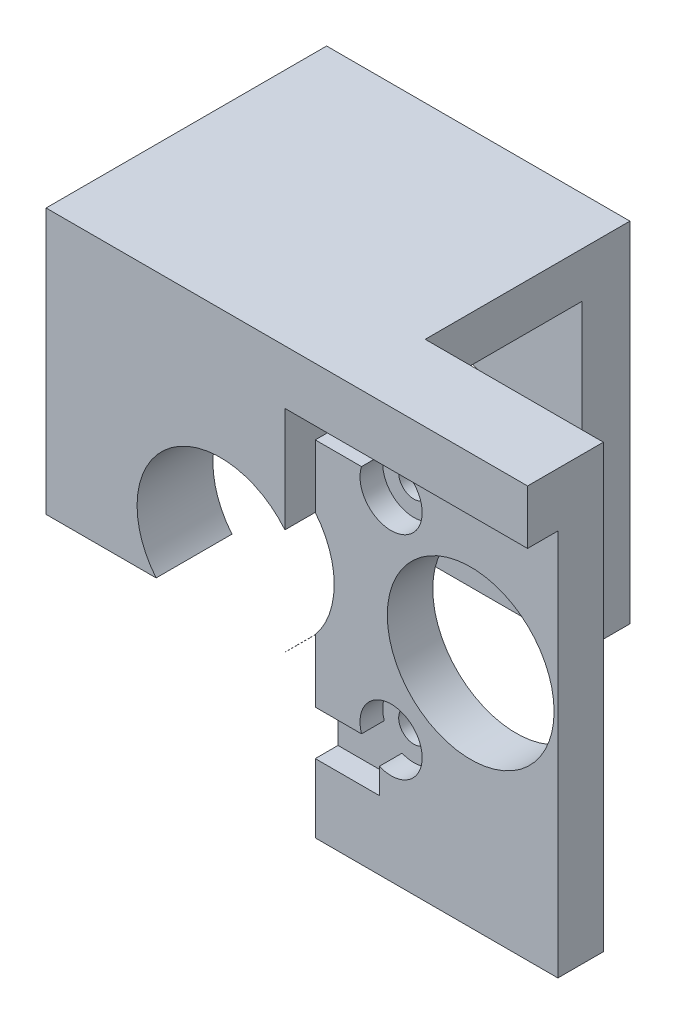
SolidWorks part; units mm, degrees
material "ABS"
ref_plane "Front Plane" through (0, 0, 0) normal (0, 0, 1) x (1, 0, 0)
ref_plane "Top Plane" through (0, 0, 0) normal (0, 1, 0) x (1, 0, 0)
ref_plane "Right Plane" through (0, 0, 0) normal (1, 0, 0) x (0, 0, -1)
sketch "Sketch1" plane through (0, 0, 0) normal (0, 0, 1) x (1, 0, 0)
  line L1 (-76.1871, 64.9281) -> (16.8129, 64.9281)
  line L2 (-76.1871, 64.9281) -> (-76.1871, -35.0719)
  line L3 (-76.1871, -35.0719) -> (16.8129, -35.0719)
  line L4 (16.8129, 64.9281) -> (16.8129, -35.0719)
  dimension "D1" = 93
  dimension "D2" = 100
extrude "Boss-Extrude2" add sketch "Sketch1" along normal blind 10 contours L1 L4 L3 L2
sketch "Sketch3" plane through (0, 0, 0) normal (0, 0, -1) x (-1, 0, 0)
  line L0 (76.1871, -35.0719) -> (-16.8129, -35.0719) construction
  line L1 (-16.8129, 64.9281) -> (-6.8129, 64.9281)
  line L2 (-16.8129, 64.9281) -> (-16.8129, -35.0719)
  line L3 (-16.8129, -35.0719) -> (-6.8129, -35.0719)
  line L4 (-6.8129, 64.9281) -> (-6.8129, -35.0719)
  line L5 (-16.8129, 64.9281) -> (-16.8129, -35.0719) construction
  dimension "D1" = 0
  dimension "D2" = 0
  dimension "D3" = 10
  dimension "D4" = 100
sketch "Sketch4" plane through (16.8129, 0, 0) normal (1, 0, 0) x (0, 0, -1)
  line L0 (-10, 64.9281) -> (-10, -35.0719) construction
  line L1 (-10, -5.0719) -> (0.01, -5.0719)
  line L2 (-10, -5.0719) -> (-10, -20.0719)
  line L3 (-10, -20.0719) -> (0.01, -20.0719)
  line L4 (0.01, -5.0719) -> (0.01, -20.0719)
  line L6 (-10, -35.0719) -> (0, -35.0719) construction
  dimension "D1" = 15
  dimension "D2" = 15
extrude "Boss-Extrude4" add sketch "Sketch4" along normal blind 24
sketch "Sketch5" plane through (0, -5.0719, 0) normal (0, 1, 0) x (1, 0, 0)
  line L0 (40.8129, -10) -> (16.8129, -10) construction
  line L2 (16.8129, 0) -> (16.8129, -10) construction
  circle A0 centre (26.8129, -5) radius 2
  dimension "D2" = 4
  dimension "D3" = 10
  dimension "D1" = 5
extrude "Cut-Extrude1" cut sketch "Sketch5" against normal blind 50
sketch "Sketch6" plane through (0, 0, 10) normal (0, 0, -1) x (-1, 0, 0)
  line L2 (76.1871, -35.0719) -> (-16.8129, -35.0719) construction
  line L3 (-16.8129, 64.9281) -> (-16.8129, -35.0719) construction
  circle A0 centre (-1.8129, -24.5719) radius 7.5
  dimension "D1" = 15
  dimension "D2" = 10.5
  dimension "D3" = 15
sketch "Sketch7" plane through (0, 0, 0) normal (0, 0, -1) x (-1, 0, 0)
  circle A0 centre (24.1871, 36.9281) radius 11
  circle A1 centre (24.1871, 36.9281) radius 9.3 construction
  dimension "D1" = 22
extrude "Cut-Extrude3" cut sketch "Sketch7" against normal blind 50
sketch "Sketch14" plane through (0, 0, 10) normal (0, 0, 1) x (1, 0, 0)
  line L0 (16.8129, 64.9281) -> (16.8129, -5.0719) construction
  line L1 (-44.6871, 15.7891) -> (16.8129, 15.7891)
  line L2 (-44.6871, 15.7891) -> (-44.6871, 57.7891)
  line L3 (-44.6871, 57.7891) -> (16.8129, 57.7891)
  line L4 (16.8129, 15.7891) -> (16.8129, 57.7891)
  dimension "D1" = 42
  dimension "D3" = 61.5
extrude "Cut-Extrude8" cut sketch "Sketch14" against normal blind 4
sketch "Sketch15" plane through (0, 0, 0) normal (0, 0, -1) x (-1, 0, 0)
  circle A0 centre (24.1871, 36.9281) radius 10
  circle A1 centre (24.1871, 36.9281) radius 11 construction
  dimension "D1" = 20
  dimension "D2" = 0
sketch "Sketch16" plane through (0, 0, 10) normal (0, 0, 1) x (1, 0, 0)
  line L0 (-43.6871, 56.9281) -> (14.3129, 56.9281) construction
  line L1 (-44.1871, 57.3281) -> (16.8129, 57.3281)
  line L2 (-44.1871, 57.3281) -> (-44.1871, 64.9281)
  line L3 (-44.1871, 64.9281) -> (16.8129, 64.9281)
  line L4 (16.8129, 57.3281) -> (16.8129, 64.9281)
  dimension "D1" = 0.4
sketch "Sketch17" plane through (0, 0, 10) normal (0, 0, 1) x (1, 0, 0)
  line L0 (16.8129, 15.7891) -> (16.8129, -5.0719) construction
  line L1 (-44.1871, 16.7281) -> (16.8129, 16.7281)
  line L2 (-44.1871, 16.7281) -> (-44.1871, -20.0719)
  line L3 (-44.1871, -20.0719) -> (16.8129, -20.0719)
  line L4 (16.8129, 16.7281) -> (16.8129, -20.0719)
  line L5 (-43.6871, 16.9281) -> (14.3129, 16.9281) construction
  line L6 (40.8129, -20.0719) -> (16.8129, -20.0719) construction
  line L9 (16.8129, -20.0719) -> (40.8129, -20.0719)
  line L10 (16.8129, -20.0719) -> (16.8129, -5.0719)
  line L11 (16.8129, -5.0719) -> (40.8129, -5.0719)
  line L12 (40.8129, -20.0719) -> (40.8129, -5.0719)
  line L13 (16.8129, -20.0719) -> (40.8129, -5.0719) construction
  line L14 (16.8129, -5.0719) -> (40.8129, -20.0719) construction
  point P16 (28.8129, -12.5719)
  dimension "D1" = 0.2
  dimension "D2" = 0
sketch "Sketch19" plane through (0, 0, 0) normal (0, 0, -1) x (-1, 0, 0)
  line L1 (-16.8129, 64.9281) -> (-16.8129, -35.0719) construction
  circle A0 centre (53.1871, 36.9281) radius 11
  circle A1 centre (24.1871, 36.9281) radius 10 construction
  dimension "D1" = 22
  dimension "D3" = 0
  dimension "D2" = 70
extrude "Cut-Extrude11" cut sketch "Sketch19" against normal blind 15
sketch "Sketch20" plane through (0, 0, 6) normal (0, 0, 1) x (1, 0, 0)
  circle A0 centre (-34.6871, 50.9281) radius 2
  circle A1 centre (5.3129, 50.9281) radius 2
  circle A2 centre (-34.6871, 22.9281) radius 2
  circle A3 centre (5.3129, 22.9281) radius 2
  arc A5 (-27.0471, 34.1316) -> (-27.0471, 39.7246) centre (-24.1871, 36.9281) ccw construction
  circle A6 centre (-24.1871, 36.9281) radius 11 construction
  dimension "D1" = 4
  dimension "D2" = 4
  dimension "D3" = 4
  dimension "D4" = 4
  dimension "D5" = 0
  dimension "D6" = 28
  dimension "D7" = 0
  dimension "D8" = 40
  dimension "D9" = 14
  dimension "D10" = 10.5
  dimension "D11" = 28
  dimension "D12" = 40
extrude "Cut-Extrude12" cut sketch "Sketch20" against normal blind 10
sketch "Sketch8" plane through (0, 64.9281, 0) normal (0, 1, 0) x (1, 0, 0)
  line L0 (-76.1871, -10) -> (16.8129, -10) construction
  line L5 (16.8129, 0) -> (12.3014, -10) construction
  line L6 (16.8129, -10) -> (7.8859, 0) construction
  line L8 (16.8129, -10) -> (16.8129, 0) construction
  line L9 (-76.1871, 0) -> (16.8129, 0) construction
  circle A0 centre (11.8129, -7) radius 1.4
  circle A1 centre (-13.1871, -7) radius 1.4
  point P4 (13.816, -6.6429)
  dimension "D1" = 25
  dimension "D2" = 5
  dimension "D3" = 2.8
  dimension "D4" = 7
  dimension "D5" = 7
sketch "Sketch21" plane through (0, 0, 0) normal (0, 0, -1) x (-1, 0, 0)
  line L1 (76.1871, 64.9281) -> (36.1871, 64.9281)
  line L2 (76.1871, 64.9281) -> (76.1871, 58.9281)
  line L3 (76.1871, 58.9281) -> (36.1871, 58.9281)
  line L4 (36.1871, 64.9281) -> (36.1871, 58.9281)
  dimension "D1" = 6
  dimension "D2" = 40
extrude "Boss-Extrude5" add sketch "Sketch21" along normal blind 27
sketch "Sketch22" plane through (0, 58.9281, 0) normal (0, -1, 0) x (1, 0, 0)
  line L0 (-76.1871, -27) -> (-76.1871, 0) construction
  line L1 (-36.1871, -27) -> (-76.1871, -27)
  line L2 (-36.1871, -27) -> (-36.1871, -20.7)
  line L3 (-36.1871, -20.7) -> (-76.1871, -20.7)
  line L4 (-76.1871, -27) -> (-76.1871, -20.7)
  dimension "D1" = 6.3
extrude "Boss-Extrude7" add sketch "Sketch22" along normal blind 40
sketch "Sketch23" plane through (0, 0, 10) normal (0, 0, 1) x (1, 0, 0)
  circle A0 centre (-53.1871, 36.9281) radius 8
  arc A1 (-44.6871, 43.9102) -> (-44.6871, 29.9459) centre (-53.1871, 36.9281) ccw construction
  dimension "D1" = 16
  dimension "D2" = 0
extrude "Cut-Extrude13" cut sketch "Sketch23" against normal blind 40
sketch "Sketch24" plane through (0, 0, 10) normal (0, 0, 1) x (1, 0, 0)
  line L1 (-76.1871, -35.0719) -> (42.0908, -35.0719)
  line L2 (-76.1871, -35.0719) -> (-76.1871, 6.7281)
  line L3 (-76.1871, 6.7281) -> (42.0908, 6.7281)
  line L4 (42.0908, -35.0719) -> (42.0908, 6.7281)
  dimension "D1" = 41.8
extrude "Cut-Extrude14" cut sketch "Sketch24" against normal blind 40
sketch "Sketch25" plane through (0, 0, 10) normal (0, 0, 1) x (1, 0, 0)
  line L5 (-44.6871, 29.9459) -> (-44.6871, 15.7891) construction
  line L6 (-76.1871, 6.7281) -> (-44.6871, 6.7281)
  line L7 (-76.1871, 6.7281) -> (-76.1871, 29.9281)
  line L8 (-76.1871, 29.9281) -> (-44.6871, 29.9281)
  line L9 (-44.6871, 6.7281) -> (-44.6871, 29.9281)
  arc A2 (-44.6871, 43.9102) -> (-44.6871, 29.9459) centre (-53.1871, 36.9281) ccw construction
  dimension "D1" = 7
extrude "Cut-Extrude15" cut sketch "Sketch25" against normal blind 20
sketch "Sketch26" plane through (0, 0, 6) normal (0, 0, 1) x (1, 0, 0)
  line L1 (-44.6871, 15.7891) -> (-36.2375, 15.7891)
  line L2 (-44.6871, 15.7891) -> (-44.6871, 21.6647)
  line L3 (-44.6871, 21.6647) -> (-36.2375, 21.6647)
  line L4 (-36.2375, 15.7891) -> (-36.2375, 21.6647)
  line L5 (-44.6871, 57.7891) -> (-36.2375, 57.7891)
  line L6 (-44.6871, 57.7891) -> (-44.6871, 52.1914)
  line L7 (-44.6871, 52.1914) -> (-36.2375, 52.1914)
  line L8 (-36.2375, 57.7891) -> (-36.2375, 52.1914)
  line L9 (6.8634, 52.1914) -> (14.3021, 52.1914)
  line L10 (6.8634, 52.1914) -> (6.8634, 57.7891)
  line L11 (6.8634, 57.7891) -> (14.3021, 57.7891)
  line L12 (14.3021, 52.1914) -> (14.3021, 57.7891)
  line L13 (6.8634, 20.9281) -> (14.3021, 20.9281)
  line L14 (6.8634, 20.9281) -> (6.8634, 15.7891)
  line L15 (6.8634, 15.7891) -> (14.3021, 15.7891)
  line L16 (14.3021, 20.9281) -> (14.3021, 15.7891)
  circle A0 centre (-34.6871, 22.9281) radius 2 construction
  circle A1 centre (-34.6871, 50.9281) radius 2 construction
  circle A2 centre (5.3129, 50.9281) radius 2 construction
  circle A3 centre (5.3129, 22.9281) radius 4
  circle A4 centre (5.3129, 50.9281) radius 4
  circle A5 centre (-34.6871, 50.9281) radius 4
  circle A6 centre (-34.6871, 22.9281) radius 4
  circle A7 centre (5.3129, 50.9281) radius 4
  circle A8 centre (5.3129, 22.9281) radius 4
  circle A9 centre (-34.6871, 50.9281) radius 4
  circle A10 centre (-34.6871, 22.9281) radius 4
  line M5 (-44.6871, 57.7891) -> (-44.6871, 43.9102)
  line M8 (-44.6871, 29.9281) -> (-44.6871, 15.7891)
  line M9 (-44.6871, 15.7891) -> (16.8129, 15.7891)
  line M11 (16.8129, 57.7891) -> (-44.6871, 57.7891)
  dimension "D1" = 8
  dimension "D2" = 8
  dimension "D3" = 8
  dimension "D4" = 8
extrude "Cut-Extrude18" cut sketch "Sketch26" against normal blind 3 contours A4 L9 L12 L10 M11 | A3 L14 L16 L13 M9 | A5 L8 L7 M11 M5 | A6 L3 L4 M8 M9 region at (-40.7189, 18.5733, 6) region at (10.7466, 18.2528, 6) region at (10.8466, 55.1634, 6) region at (-40.7326, 55.141, 6)
sketch "Sketch27" plane through (0, 0, 6) normal (0, 0, 1) x (1, 0, 0)
  circle A0 centre (5.3129, 50.9281) radius 4.1
  circle A1 centre (5.3129, 22.9281) radius 4
  circle A2 centre (-34.6871, 50.9281) radius 4.1
  circle A3 centre (-34.6871, 22.9281) radius 4.1
  dimension "D1" = 8.2
  dimension "D2" = 8.2
  dimension "D3" = 8
  dimension "D4" = 8.2
extrude "Cut-Extrude29" cut sketch "Sketch27" against normal blind 3
sketch "Sketch28" plane through (0, 0, 0) normal (0, 0, -1) x (-1, 0, 0)
  line L5 (-16.8129, 6.7281) -> (44.6871, 6.7281) construction
  line L6 (-16.8129, 64.9281) -> (12.6871, 64.9281)
  line L7 (-16.8129, 64.9281) -> (-16.8129, 6.7281)
  line L8 (-16.8129, 6.7281) -> (12.6871, 6.7281)
  line L9 (12.6871, 64.9281) -> (12.6871, 6.7281)
  circle A1 centre (34.6871, 22.9281) radius 2 construction
  dimension "D1" = 22
extrude "Cut-Extrude30" cut sketch "Sketch28" against normal blind 23
sketch "Sketch29" plane through (0, 15.7891, 0) normal (0, 1, 0) x (1, 0, 0)
  line L1 (-44.6871, -10) -> (-12.6871, -10)
  line L2 (-44.6871, -10) -> (-44.6871, -6)
  line L3 (-44.6871, -6) -> (-12.6871, -6)
  line L4 (-12.6871, -10) -> (-12.6871, -6)
extrude "Cut-Extrude31" cut sketch "Sketch29" against normal blind 23
